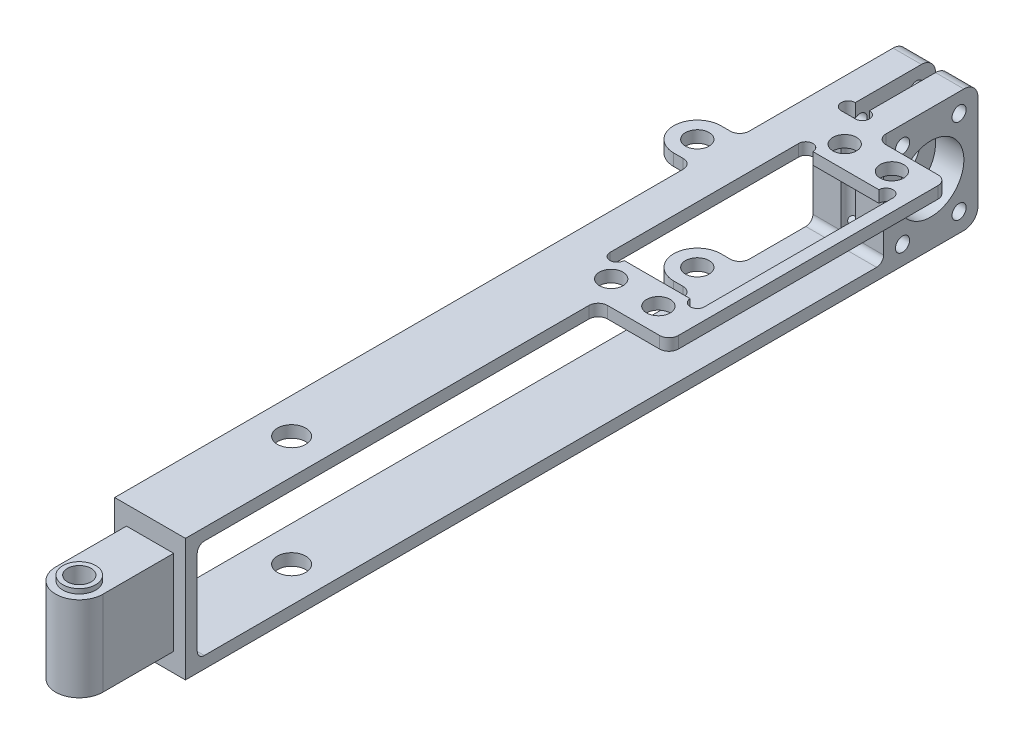
SolidWorks part; units mm, degrees
material "6061 合金"
ref_plane "前视基准面" through (0, 0, 0) normal (0, 0, 1) x (1, 0, 0)
ref_plane "上视基准面" through (0, 0, 0) normal (0, 1, 0) x (1, 0, 0)
ref_plane "右视基准面" through (0, 0, 0) normal (1, 0, 0) x (0, 0, -1)
sketch "草图1" plane through (0, 0, 0) normal (0, 0, 1) x (1, 0, 0)
  line L1 (0, 0) -> (15, 0)
  line L2 (0, 0) -> (0, 26)
  line L3 (0, 26) -> (15, 26)
  line L4 (15, 0) -> (15, 26)
  dimension "D1" = 26
  dimension "D2" = 15
extrude "凸台-拉伸1" add sketch "草图1" along normal blind 168
ref_plane "基准面1" through (0, 13, 0) normal (0, 1, 0) x (1, 0, 0)
sketch "草图2" plane through (0, 13, 0) normal (0, 1, 0) x (1, 0, 0)
  line L0 (7.5, -168) -> (7.5, 0) construction
  line L1 (15, -168) -> (0, -168) construction
  line L2 (15, 0) -> (0, 0) construction
  line L3 (12.5, -183) -> (12.5, -168)
  line L4 (12.5, -168) -> (2.5, -168)
  line L5 (2.5, -168) -> (2.5, -183)
  circle A0 centre (7.5, -183) radius 2.5
  arc A1 (2.5, -183) -> (12.5, -183) centre (7.5, -183) ccw
  dimension "D1" = 5
  dimension "D2" = 10
  dimension "D3" = 15
extrude "凸台-拉伸2" add sketch "草图2" along normal mid plane 18
sketch "草图3" plane through (0, 22, 0) normal (0, 1, 0) x (1, 0, 0)
  circle A0 centre (7.5, -183) radius 3.5
  circle A1 centre (7.5, -183) radius 2.5
  dimension "D1" = 7
  dimension "D2" = 5
extrude "凸台-拉伸3" add sketch "草图3" along normal blind 1 and the other way blind 19
sketch "草图4" plane through (15, 0, 0) normal (1, 0, 0) x (0, 0, -1)
  line L0 (-168, 22) -> (-168, 4) construction
  line L1 (-165.5, 23.5) -> (-80.5, 23.5)
  line L2 (-165.5, 23.5) -> (-165.5, 2.5)
  line L3 (-165.5, 2.5) -> (-80.5, 2.5)
  line L4 (-80.5, 23.5) -> (-80.5, 2.5)
  line L5 (-168, 0) -> (0, 0) construction
  line L6 (-168, 26) -> (0, 26) construction
  dimension "D1" = 2.5
  dimension "D2" = 2.5
  dimension "D3" = 2.5
  dimension "D4" = 85
extrude "切除-拉伸1" cut sketch "草图4" against normal blind 24
sketch "草图5" plane through (0, 26, 0) normal (0, 1, 0) x (1, 0, 0)
  line L0 (15, 0) -> (0, 0) construction
  line L1 (6, 0) -> (9, 0)
  line L2 (6, 0) -> (6, -17)
  line L3 (6, -20) -> (9, -20)
  line L4 (9, 0) -> (9, -17)
  line L5 (0, -168) -> (0, 0) construction
  arc A0 (6, -17) -> (6, -20) centre (6, -18.5) ccw
  arc A1 (9, -20) -> (9, -17) centre (9, -18.5) ccw
  dimension "D4" = 3
  dimension "D1" = 3
  dimension "D2" = 20
  dimension "D3" = 6
extrude "切除-拉伸2" cut sketch "草图5" against normal blind 33
sketch "草图6" plane through (15, 0, 0) normal (1, 0, 0) x (0, 0, -1)
  line L1 (-78, 23.5) -> (0, 23.5)
  line L2 (-78, 23.5) -> (-78, 2.5)
  line L3 (-78, 2.5) -> (0, 2.5)
  line L4 (0, 23.5) -> (0, 2.5)
  line L5 (-168, 26) -> (0, 26) construction
  line L6 (0, 0) -> (0, 26) construction
  line L7 (-168, 0) -> (0, 0) construction
  line L8 (-80.5, 2.5) -> (-80.5, 23.5) construction
  dimension "D1" = 2.5
  dimension "D2" = 2.5
  dimension "D3" = 2.5
extrude "切除-拉伸3" cut sketch "草图6" against normal blind 33
sketch "草图7" plane through (0, 26, 0) normal (0, 1, 0) x (1, 0, 0)
  line L0 (15, -168) -> (15, 0) construction
  line L1 (15, -21.5) -> (30, -21.5)
  line L2 (15, -21.5) -> (15, -80.5)
  line L3 (15, -80.5) -> (30, -80.5)
  line L4 (30, -21.5) -> (30, -80.5)
  line L5 (15, -168) -> (0, -168) construction
  dimension "D1" = 15
  dimension "D2" = 59
  dimension "D3" = 87.5
extrude "凸台-拉伸4" add sketch "草图7" against normal blind 26
sketch "草图8" plane through (0, 26, 0) normal (0, 1, 0) x (1, 0, 0)
  line L0 (6, 0) -> (6, -17) construction
  line L1 (10.5, -30.5) -> (24.5, -30.5)
  line L2 (7.5, -30.5) -> (7.5, -70.5)
  line L3 (10.5, -70.5) -> (24.5, -70.5)
  line L4 (27.5, -30.5) -> (27.5, -70.5)
  line L5 (15, -80.5) -> (30, -80.5) construction
  arc A0 (10.5, -30.5) -> (7.5, -30.5) centre (9, -30.5) ccw
  arc A1 (27.5, -30.5) -> (24.5, -30.5) centre (26, -30.5) ccw
  arc A2 (7.5, -70.5) -> (10.5, -70.5) centre (9, -70.5) ccw
  arc A3 (24.5, -70.5) -> (27.5, -70.5) centre (26, -70.5) ccw
  circle A4 centre (12.5, -25.75) radius 2.5
  circle A5 centre (22.5, -25.75) radius 2.5
  circle A6 centre (12.5, -75.25) radius 2.5
  circle A7 centre (22.5, -75.25) radius 2.5
  point P4 (7.5, -50.5)
  point P25 (0, 0)
  point P26 (0, 0)
  point P27 (0, 0)
  point P28 (0, 0)
  point P29 (0, 0)
  dimension "D5" = 3
  dimension "D6" = 3
  dimension "D7" = 3
  dimension "D8" = 3
  dimension "D9" = 5
  dimension "D10" = 5
  dimension "D11" = 5
  dimension "D12" = 5
  dimension "D13" = 10
  dimension "D14" = 49.5
  dimension "D15" = 5
  dimension "D16" = 4.75
  dimension "D1" = 20
  dimension "D2" = 40
  dimension "D3" = 1.5
  dimension "D4" = 10
extrude "切除-拉伸4" cut sketch "草图8" against normal blind 23.5
sketch "草图9" plane through (0, 26, 0) normal (0, 1, 0) x (1, 0, 0)
  line L0 (7.5, -30.5) -> (7.5, -70.5) construction
  line L5 (24.5, -30.5) -> (10.5, -30.5) construction
  line L6 (-4, -35.5) -> (1, -35.5)
  line L7 (1, -35.5) -> (1, -45.5)
  line L8 (1, -45.5) -> (-4, -45.5)
  circle A0 centre (-4, -40.5) radius 2.5
  arc A1 (-4, -35.5) -> (-4, -45.5) centre (-4, -40.5) ccw
  dimension "D1" = 5
  dimension "D2" = 10
  dimension "D3" = 11.5
  dimension "D4" = 10
extrude "凸台-拉伸5" add sketch "草图9" against normal blind 2.5
sketch "草图10" plane through (0, 0, 0) normal (0, -1, 0) x (1, 0, 0)
  line L0 (-4, 45.5) -> (1, 45.5)
  line L1 (1, 45.5) -> (1, 35.5)
  line L2 (1, 35.5) -> (-4, 35.5)
  circle A0 centre (-4, 40.5) radius 2.5
  arc A1 (-4, 45.5) -> (-4, 35.5) centre (-4, 40.5) ccw
  dimension "D1" = 5
  dimension "D2" = 10
extrude "凸台-拉伸6" add sketch "草图10" against normal blind 2.5
sketch "草图11" plane through (0, 0, 0) normal (0, -1, 0) x (1, 0, 0)
  line L0 (15, 168) -> (15, 80.5) construction
  circle A0 centre (7.5, 138) radius 3
  circle A1 centre (7.5, 183) radius 2.5 construction
  dimension "D1" = 6
  dimension "D2" = 45
  dimension "D3" = 7.5
extrude "切除-拉伸5" cut sketch "草图11" against normal blind 82.5
sketch "草图12" plane through (15, 0, 0) normal (-1, 0, 0) x (0, 0, 1)
  line L1 (21.5, 23.5) -> (78, 23.5)
  line L2 (21.5, 23.5) -> (21.5, 2.5)
  line L3 (21.5, 2.5) -> (78, 2.5)
  line L4 (78, 23.5) -> (78, 2.5)
extrude "切除-拉伸6" cut sketch "草图12" against normal blind 82.5
sketch "草图13" plane through (0, 0, 0) normal (0, -1, 0) x (1, 0, 0)
  line L1 (15, 80.5) -> (30, 80.5)
  line L2 (15, 80.5) -> (15, 21.5)
  line L3 (15, 21.5) -> (30, 21.5)
  line L4 (30, 80.5) -> (30, 21.5)
extrude "切除-拉伸7" cut sketch "草图13" against normal blind 23.5
sketch "草图14" plane through (0, 0, 78) normal (0, 0, -1) x (-1, 0, 0)
  line L1 (-15, 23.5) -> (0, 23.5)
  line L2 (-15, 23.5) -> (-15, 2.5)
  line L3 (-15, 2.5) -> (0, 2.5)
  line L4 (0, 23.5) -> (0, 2.5)
  point P4 (0, 0)
  point P5 (0, 0)
  point P8 (0, 2.5)
extrude "切除-拉伸8" cut sketch "草图14" against normal blind 23.5
sketch "草图15" plane through (0, 0, 0) normal (0, -1, 0) x (1, 0, 0)
  line L0 (0, 35.5) -> (0, 0) construction
  line L1 (0, 20) -> (6, 20)
  line L2 (0, 20) -> (0, 0)
  line L3 (0, 0) -> (6, 0)
  line L4 (6, 17) -> (6, 0)
  line L5 (9, 17) -> (9, 0) construction
  line L6 (9, 20) -> (15, 20)
  line L7 (9, 17) -> (9, 0)
  line L8 (9, 0) -> (15, 0)
  line L9 (15, 20) -> (15, 0)
  line L10 (6, 20) -> (9, 20) construction
  arc A0 (9, 17) -> (9, 20) centre (9, 18.5) ccw
  arc A1 (6, 20) -> (6, 17) centre (6, 18.5) ccw
  point P17 (9, 0)
  point P18 (9.5301, 17)
  point P22 (9, 18.5)
  point P23 (9, 18.5)
  point P25 (0, 0)
  point P26 (9, 17)
  dimension "D1" = 3
  dimension "D2" = 3
extrude "凸台-拉伸7" add sketch "草图15" against normal blind 23.5
fillet "圆角1" radius 2 8 edges at (15, 24.75, 21.5) (30, 24.75, 21.5) (30, 24.75, 80.5) (15, 24.75, 80.5) (0, 1.25, 45.5) (0, 1.25, 35.5) (0, 24.75, 35.5) (0, 24.75, 45.5)
sketch "草图16" plane through (0, 0, 0) normal (-1, 0, 0) x (0, 0, 1)
  line L0 (33.5, 0) -> (0, 0) construction
  line L1 (0, 26) -> (0, 0) construction
  line L2 (16, 4) -> (4, 22) construction
  line L3 (16, 22) -> (4, 4) construction
  circle A0 centre (4, 4) radius 1.5
  circle A1 centre (16, 4) radius 1.5
  circle A2 centre (4, 22) radius 1.5
  circle A3 centre (16, 22) radius 1.5
  circle A4 centre (10, 13) radius 7
  dimension "D1" = 18
  dimension "D2" = 4
  dimension "D3" = 3
  dimension "D4" = 12
  dimension "D5" = 4
  dimension "D6" = 14
extrude "切除-拉伸9" cut sketch "草图16" against normal blind 23.5
fillet "圆角2" radius 1.5 4 edges at (7.5, 23.5, 165.5) (7.5, 2.5, 165.5) (12, 2.5, 20) (12, 23.5, 20)
fillet "圆角3" radius 3 2 edges at (3, 26, 0) (3, 0, 0)
